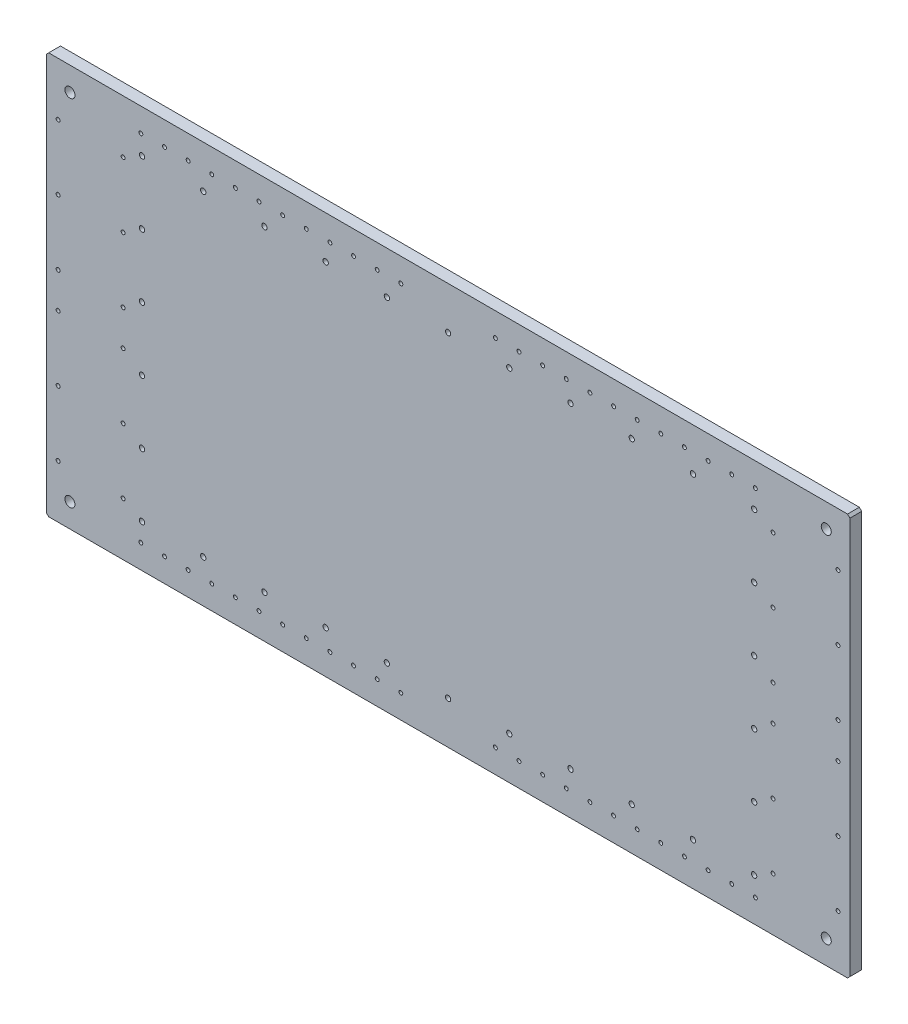
SolidWorks part; units mm, degrees
ref_plane "Front Plane" through (0, 0, 0) normal (0, 0, 1) x (1, 0, 0)
ref_plane "Top Plane" through (0, 0, 0) normal (0, 1, 0) x (1, 0, 0)
ref_plane "Right Plane" through (0, 0, 0) normal (1, 0, 0) x (0, 0, -1)
sketch "Sketch1" plane through (0, 0, 0) normal (0, 0, 1) x (1, 0, 0)
  line L0 (265, 8.25) -> (265, 140)
  line L1 (0, 0) -> (265, 0)
  line L2 (0, 0) -> (0, 140)
  line L3 (0, 140) -> (265, 140)
  line L4 (265, 0) -> (265, 3.75)
  circle A0 centre (6, 113.2) radius 2.25
  circle A1 centre (6, 59.6) radius 2.25
  circle A2 centre (6, 6) radius 2.25
  circle A3 centre (57.8, 6) radius 2.25
  circle A4 centre (109.6, 6) radius 2.25
  circle A5 centre (161.4, 6) radius 2.25
  circle A6 centre (213.2, 6) radius 2.25
  arc A7 (265, 8.25) -> (265, 3.75) centre (265, 6) ccw
  dimension "D3" = 4.5
  dimension "D4" = 4.5
  dimension "D5" = 4.5
  dimension "D6" = 4.5
  dimension "D7" = 4.5
  dimension "D8" = 4.5
  dimension "D9" = 4.5
  dimension "D10" = 6
  dimension "D11" = 6
  dimension "D12" = 6
  dimension "D13" = 6
  dimension "D14" = 6
  dimension "D15" = 6
  dimension "D16" = 6
  dimension "D17" = 6
  dimension "D18" = 4.5
  dimension "D19" = 6
  dimension "D20" = 51.8
  dimension "D21" = 51.8
  dimension "D22" = 51.8
  dimension "D23" = 51.8
  dimension "D24" = 53.6
  dimension "D25" = 53.6
  dimension "D1" = 265
  dimension "D2" = 140
extrude "Boss-Extrude1" add sketch "Sketch1" along normal blind 10 contours L1 L4 A7 L0 L3 L2 | A4 | A5 | A6 | A3 | A2 | A1 | A0
sketch "Sketch2" plane through (0, 0, 0) normal (-1, 0, 0) x (0, 0, 1)
  line L1 (0, 140) -> (10, 140)
  line L2 (0, 140) -> (0, 0)
  line L3 (0, 0) -> (10, 0)
  line L4 (10, 140) -> (10, 0)
extrude "Boss-Extrude2" add sketch "Sketch2" along normal blind 75
sketch "Sketch3" plane through (0, 0, 0) normal (0, -1, 0) x (1, 0, 0)
  line L1 (-75, 0) -> (265, 0)
  line L2 (-75, 0) -> (-75, 10)
  line L3 (-75, 10) -> (265, 10)
  line L4 (265, 0) -> (265, 10)
extrude "Boss-Extrude3" add sketch "Sketch3" along normal blind 30
sketch "Sketch4" plane through (0, 0, 10) normal (0, 0, 1) x (1, 0, 0)
  line L0 (-75, -30) -> (-75, 140) construction
  line L1 (265, -30) -> (-75, -30) construction
  circle A0 centre (-55, -10) radius 4.2 construction
  dimension "D1" = 8.4
  dimension "D2" = 20
  dimension "D3" = 20
sketch "Sketch9" plane through (0, 0, 10) normal (0, 0, 1) x (1, 0, 0)
  line L0 (-75, 140) -> (265, 140) construction
  line L1 (265, -30) -> (265, 3.75) construction
  circle A0 centre (225, -10) radius 1.65
  dimension "D1" = 150
  dimension "D2" = 40
  dimension "D3" = 3.3
hole_wizard "M10x1.5 Tapped Hole1" positions "3DSketch1" profile "Sketch14" tap size "M10x1.5" standard "BSI" end condition through all
sketch3d "3DSketch1"
  point P0 (-55, -10, 10)
sketch "Sketch14" plane through (-55, -10, 10) normal (1, 0, 0) x (0, -1, 0)
  line L0 (0, 0) -> (0, 10)
  line L1 (0, 10) -> (4.25, 10)
  line L2 (4.25, 10) -> (4.25, 0)
  line L5 (4.25, 0) -> (0, 0)
  line L11 (0, -6.35) -> (0, 107.95) construction
  dimension "Thru Tap Drill Dia." = 8.5
  dimension "Thru Tap Drill Depth" = 10
cosmetic thread "Hole Thread1" parameters "D2"=10
hole_wizard "M4x0.7 Tapped Hole1" positions "3DSketch2" profile "Sketch15" tap size "M4x0.7" standard "BSI" end condition through all
sketch3d "3DSketch2"
  point P0 (225, -10, 10)
sketch "Sketch15" plane through (225, -10, 10) normal (1, 0, 0) x (0, -1, 0)
  line L0 (0, 0) -> (0, 10)
  line L1 (0, 10) -> (1.65, 10)
  line L2 (1.65, 10) -> (1.65, 0)
  line L5 (1.65, 0) -> (0, 0)
  line L11 (0, -6.35) -> (0, 107.95) construction
  dimension "Thru Tap Drill Dia." = 3.3
  dimension "Thru Tap Drill Depth" = 10
cosmetic thread "Hole Thread2" parameters "D2"=4
pattern_linear "LPattern1" count 12 spacing 20 along (-1, 0, 0) of "M4x0.7 Tapped Hole1"
sketch "Sketch13" plane through (0, 0, 10) normal (0, 0, 1) x (1, 0, 0)
  line L0 (-75, -30) -> (-75, 140) construction
  line L1 (-75, 140) -> (265, 140) construction
  circle A0 centre (-65, 125) radius 1.65
  circle A2 centre (-10, 125) radius 1.65
  circle A3 centre (-65, 70) radius 1.65
  circle A4 centre (-10, 70) radius 1.65
  circle A5 centre (-65, 15) radius 1.65
  circle A6 centre (-10, 15) radius 1.65
  dimension "D1" = 3.3
  dimension "D3" = 3.3
  dimension "D4" = 10
  dimension "D9" = 15
  dimension "D12" = 15
  dimension "D2" = 55
  dimension "D5" = 3
hole_wizard "M4x0.7 Tapped Hole2" positions "3DSketch3" profile "Sketch16" tap size "M4x0.7" standard "BSI" end condition through all
sketch3d "3DSketch3"
  point P0 (-10, 125, 10)
  point P3 (-10, 70, 10)
  point P6 (-10, 15, 10)
  point P9 (-65, 125, 10)
  point P12 (-65, 70, 10)
  point P15 (-65, 15, 10)
sketch "Sketch16" plane through (-10, 125, 10) normal (1, 0, 0) x (0, -1, 0)
  line L0 (0, 0) -> (0, 10)
  line L1 (0, 10) -> (1.65, 10)
  line L2 (1.65, 10) -> (1.65, 0)
  line L5 (1.65, 0) -> (0, 0)
  line L11 (0, -6.35) -> (0, 107.95) construction
  dimension "Thru Tap Drill Dia." = 3.3
  dimension "Thru Tap Drill Depth" = 10
cosmetic thread "Hole Thread3" parameters "D2"=4
cosmetic thread "Hole Thread4" parameters "D2"=4
cosmetic thread "Hole Thread5" parameters "D2"=4
cosmetic thread "Hole Thread6" parameters "D2"=4
cosmetic thread "Hole Thread7" parameters "D2"=4
cosmetic thread "Hole Thread8" parameters "D2"=4
chamfer "Chamfer1" distance 2.5 angle 45 8 edges at (262.75, 6, 0) (215.45, 6, 0) (163.65, 6, 0) (111.85, 6, 0) (60.05, 6, 0) (8.25, 6, 0) (8.25, 59.6, 0) (8.25, 113.2, 0)
mirror "Mirror1" about plane through (265, 8.25, 10) normal (-1, 0, 0) of bodies 121 115
mirror "Mirror2" about plane through (0, 140, 10) normal (0, 1, 0) of bodies 116
ref_plane "Plane9" through (265, 0, 0) normal (1, 0, 0) x (0, 0, -1)
ref_plane "Plane10" through (0, 140, 0) normal (0, -1, 0) x (-1, 0, 0)
mirror "Mirror3" about plane through (265, 0, 0) normal (1, 0, 0) of "LPattern1", "M4x0.7 Tapped Hole2", "M4x0.7 Tapped Hole1", "M10x1.5 Tapped Hole1"
mirror "Mirror4" about plane through (0, 140, 0) normal (0, -1, 0) of "Mirror3"
chamfer "Chamfer2" distance 2 angle 45 4 edges at (-75, -30, 5) (-75, 310, 5) (605, 310, 5) (605, -30, 5)
equation "\"D3@Sketch13\"=\"D1@Sketch13\""
equation "\"D12@Sketch13\"=\"D9@Sketch13\""
